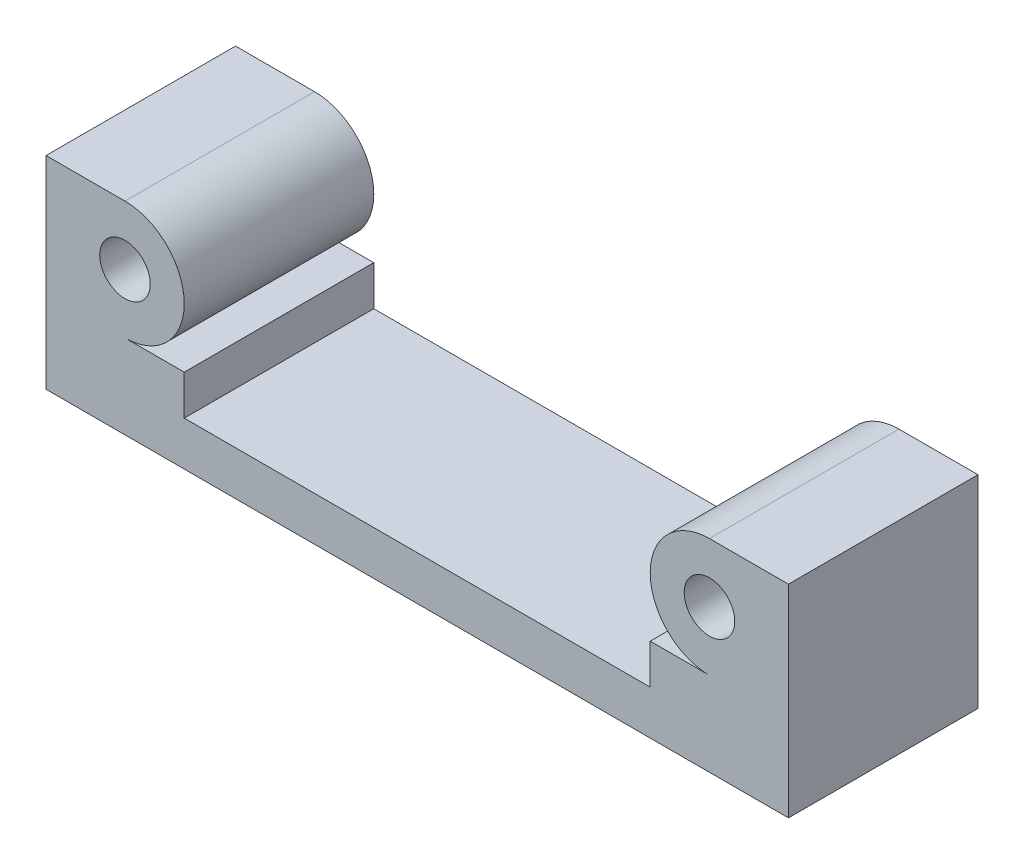
SolidWorks part; units mm, degrees
ref_plane "Front Plane" through (0, 0, 0) normal (0, 0, 1) x (1, 0, 0)
ref_plane "Top Plane" through (0, 0, 0) normal (0, 1, 0) x (1, 0, 0)
ref_plane "Right Plane" through (0, 0, 0) normal (1, 0, 0) x (0, 0, -1)
sketch "Sketch1" plane through (0, 0, 0) normal (0, 0, 1) x (1, 0, 0)
  line L0 (-3.75, 10.0231) -> (-8.75, 10.0231)
  line L1 (-8.75, 10.0231) -> (-8.75, -2.7924)
  line L2 (-8.75, -2.7924) -> (38.25, -2.7924)
  line L3 (38.25, -2.7924) -> (38.25, 10.0231)
  line L4 (38.25, 10.0231) -> (33.25, 10.0231)
  line L5 (29.5, 0) -> (29.5, 2.5231) construction
  line L6 (33.25, 2.5231) -> (38.25, 2.5231)
  line L7 (-3.75, 2.5231) -> (-8.75, 2.5231)
  line L8 (-55.8397, -2.7924) -> (65.7397, -2.7924) construction
  line L10 (-3.75, 2.5231) -> (0, 2.5231)
  line L11 (0, 2.5231) -> (0, 0)
  line L12 (0, 0) -> (29.5, 0)
  line L13 (29.5, 0) -> (29.5, 2.5231)
  line L14 (29.5, 2.5231) -> (33.25, 2.5231)
  circle A0 centre (-3.75, 6.2731) radius 1.6
  circle A1 centre (-3.75, 6.2731) radius 3.75
  circle A2 centre (33.25, 6.2731) radius 1.6
  circle A3 centre (33.25, 6.2731) radius 3.75
  circle A4 centre (33.25, 6.2731) radius 3.75
  dimension "D1" = 5
  dimension "D2" = 5
extrude "Boss-Extrude1" add sketch "Sketch1" along normal up to surface (12 mm away) contours A1 A0 | A3 A2 | A1 L0 L1 L7 | A3 L6 L3 L4 | L2 L3 | L7 L1 L2 region at (-7.5522, 6.2731, 0) region at (-1.1733, 8.8498, 0) region at (14.75, -0.7271, 0) region at (37.0522, 6.2731, 0) region at (29.6061, 6.2731, 0)
